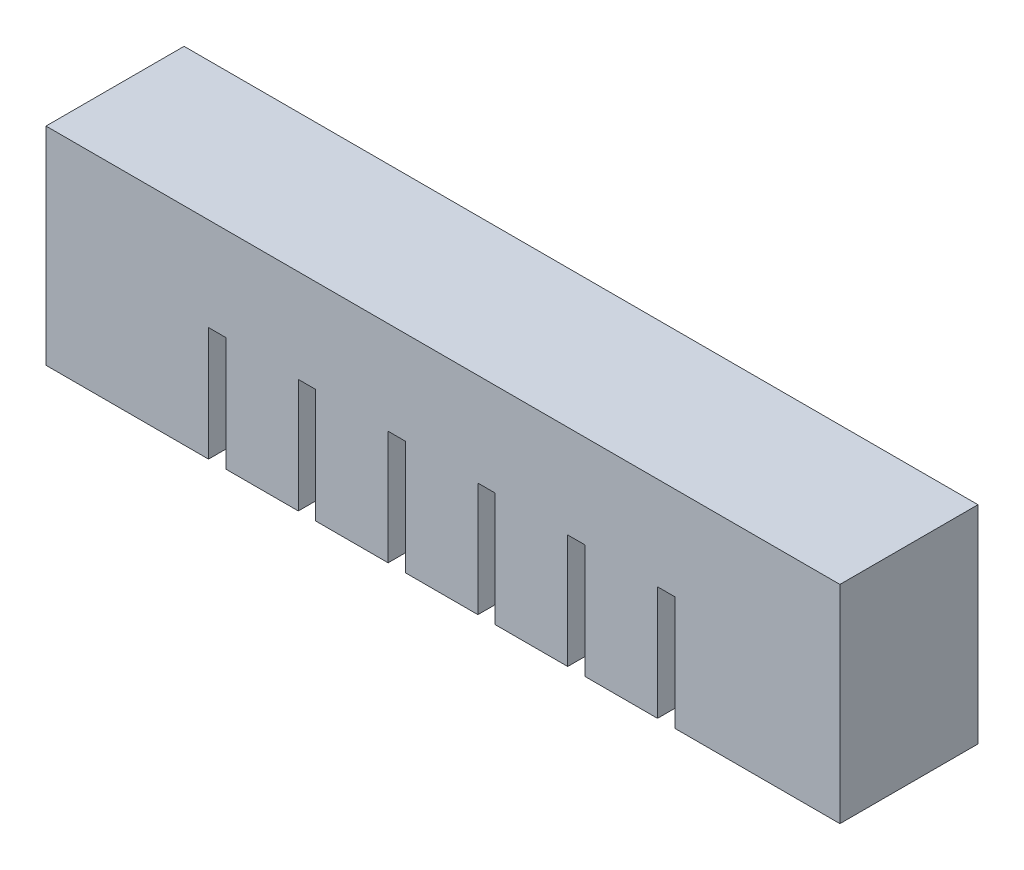
SolidWorks part; units mm, degrees
ref_plane "前视基准面" through (0, 0, 0) normal (0, 0, 1) x (1, 0, 0)
ref_plane "上视基准面" through (0, 0, 0) normal (0, 1, 0) x (1, 0, 0)
ref_plane "右视基准面" through (0, 0, 0) normal (1, 0, 0) x (0, 0, -1)
other "Configuration Table"
sketch "草图1" plane through (0, 0, 0) normal (0, 0, 1) x (1, 0, 0)
  line L0 (0, 0) -> (0, 30.0155)
  line L1 (0, 30.0155) -> (-115, 30.0155)
  line L2 (-115, 30.0155) -> (-115, 0)
  line L3 (-115, 0) -> (-95.0492, 0)
  line L4 (-95.0492, 0) -> (-91.458, 0)
  line L5 (-91.458, 0) -> (-91.458, 16.5085)
  line L6 (-91.458, 16.5085) -> (-88.9567, 16.5085)
  line L7 (-88.9567, 16.5085) -> (-88.9567, 0)
  line L8 (-88.9567, 0) -> (-78.4512, 0)
  line L9 (-78.4512, 0) -> (-78.4512, 16.5085)
  line L10 (-78.4512, 16.5085) -> (-75.9499, 16.5085)
  line L11 (-75.9499, 16.5085) -> (-75.9499, 0)
  line L12 (-75.9499, 0) -> (-65.4445, 0)
  line L13 (-65.4445, 0) -> (-65.4445, 16.5085)
  line L14 (-65.4445, 16.5085) -> (-62.9432, 16.5085)
  line L15 (-62.9432, 16.5085) -> (-62.9432, 0)
  line L16 (-62.9432, 0) -> (-52.4378, 0)
  line L17 (-52.4378, 0) -> (-52.4378, 16.5085)
  line L18 (-52.4378, 16.5085) -> (-49.9365, 16.5085)
  line L19 (-49.9365, 16.5085) -> (-49.9365, 0)
  line L20 (-49.9365, 0) -> (-39.431, 0)
  line L21 (-39.431, 0) -> (-39.431, 16.5085)
  line L22 (-39.431, 16.5085) -> (-36.9297, 16.5085)
  line L23 (-36.9297, 16.5085) -> (-36.9297, 0)
  line L24 (-36.9297, 0) -> (-26.4243, 0)
  line L25 (-26.4243, 0) -> (-26.4243, 16.5085)
  line L26 (-26.4243, 16.5085) -> (-23.923, 16.5085)
  line L27 (-23.923, 16.5085) -> (-23.923, 0)
  line L28 (-23.923, 0) -> (0, 0)
  dimension "D1" = 115
extrude "凸台-拉伸1" add sketch "草图1" along normal blind 10 and the other way blind 10
sketch "草图2" plane through (0, 0, 0) normal (0, 0, 1) x (1, 0, 0)
  line L0 (-99, 22) -> (-99, 8.5)
  line L1 (-99, 8.5) -> (-94, 8.5)
  line L2 (-94, 8.5) -> (-94, 19.5)
  line L3 (-94, 19.5) -> (-86, 19.5)
  line L4 (-86, 19.5) -> (-86, 8.5)
  line L5 (-86, 8.5) -> (-81, 8.5)
  line L6 (-81, 8.5) -> (-81, 19.5)
  line L7 (-81, 19.5) -> (-73, 19.5)
  line L8 (-73, 19.5) -> (-73, 8.5)
  line L9 (-73, 8.5) -> (-68, 8.5)
  line L10 (-68, 8.5) -> (-68, 19.5)
  line L11 (-68, 19.5) -> (-60, 19.5)
  line L12 (-60, 19.5) -> (-60, 8.5)
  line L13 (-60, 8.5) -> (-55, 8.5)
  line L14 (-55, 8.5) -> (-55, 19.5)
  line L15 (-55, 19.5) -> (-47, 19.5)
  line L16 (-47, 19.5) -> (-47, 8.5)
  line L17 (-47, 8.5) -> (-42, 8.5)
  line L18 (-42, 8.5) -> (-42, 19.5)
  line L19 (-42, 19.5) -> (-34, 19.5)
  line L20 (-34, 19.5) -> (-34, 8.5)
  line L21 (-34, 8.5) -> (-29, 8.5)
  line L22 (-29, 8.5) -> (-29, 19.5)
  line L23 (-29, 19.5) -> (-21, 19.5)
  line L24 (-21, 19.5) -> (-21, 8.5)
  line L25 (-21, 8.5) -> (-16, 8.5)
  line L26 (-16, 8.5) -> (-16, 22)
  line L27 (-16, 22) -> (-99, 22)
extrude "凸台-拉伸2" add sketch "草图2" along normal blind 7.5 and the other way blind 7.5 separate body
